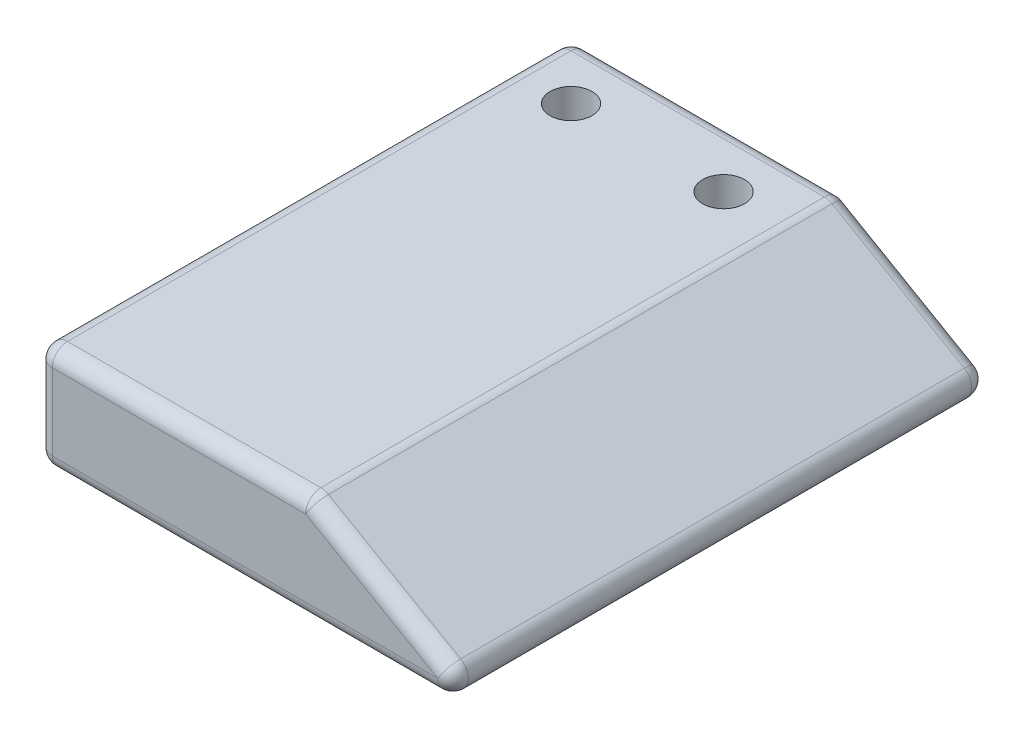
SolidWorks part; units mm, degrees
ref_plane "Front Plane" through (0, 0, 0) normal (0, 0, 1) x (1, 0, 0)
ref_plane "Top Plane" through (0, 0, 0) normal (0, 1, 0) x (1, 0, 0)
ref_plane "Right Plane" through (0, 0, 0) normal (1, 0, 0) x (0, 0, -1)
sketch "Sketch1" plane through (0, 0, 0) normal (0, 0, 1) x (1, 0, 0)
  line L0 (0, 0) -> (0, 14)
  line L1 (0, 14) -> (35.7513, 14)
  line L2 (35.7513, 14) -> (60, 0)
  line L3 (60, 0) -> (0, 0)
  dimension "D1" = 60
  dimension "D2" = 30
  dimension "D3" = 14
extrude "Boss-Extrude1" add sketch "Sketch1" along normal blind 70
hole_wizard "CSK for M5 Hex Socket Countersunk Cap Screw1" positions "Sketch2" profile "Sketch3" countersink size "M5" standard "ISO" end condition through all
sketch "Sketch2" plane through (0, 0, 0) normal (0, -1, 0) x (-1, 0, 0)
  line L0 (0, 0) -> (-60, 0) construction
  line L1 (0, -70) -> (0, 0) construction
  point P0 (-8, -8)
  point P2 (-28, -8)
  dimension "D1" = 8
  dimension "D2" = 8
  dimension "D3" = 20
sketch "Sketch3" plane through (8, 0, 8) normal (1, 0, 0) x (0, 0, -1)
  line L0 (0, 0) -> (0, 14)
  line L1 (0, 14) -> (2.75, 14)
  line L2 (2.75, 14) -> (2.75, 2.85)
  line L3 (2.75, 2.85) -> (5.6, 0)
  line L5 (5.6, 0) -> (0, 0)
  line L6 (-2.75, 2.85) -> (-5.6, 0) construction
  line L11 (0, -6.35) -> (0, 107.95) construction
  dimension "Thru Hole Dia." = 5.5
  dimension "Thru Hole Depth" = 14
  dimension "Near C'Sink Dia." = 11.2
  dimension "Near C'Sink Angle" = 90
fillet "Fillet1" radius 2 12 edges at (60, 0, 35) (35.7513, 14, 35) (47.8756, 7, 0) (17.8756, 14, 0) (30, 0, 0) (17.8756, 14, 70) (47.8756, 7, 70) (30, 0, 70) (0, 14, 35) (0, 7, 70) (0, 0, 35) (0, 7, 0)
